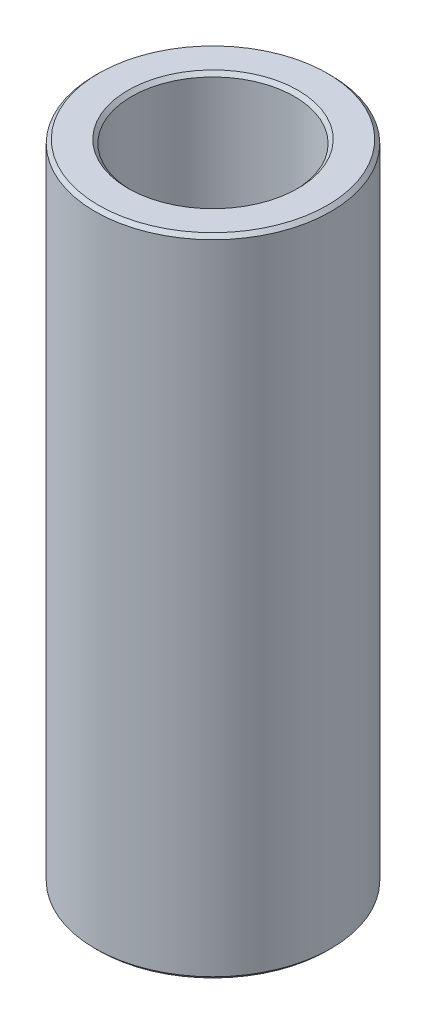
SolidWorks part; units mm, degrees
ref_plane "Front Plane" through (0, 0, 0) normal (0, 0, 1) x (1, 0, 0)
ref_plane "Top Plane" through (0, 0, 0) normal (0, 1, 0) x (1, 0, 0)
ref_plane "Right Plane" through (0, 0, 0) normal (1, 0, 0) x (0, 0, -1)
sketch "Sketch1" plane through (0, 0, 0) normal (0, 1, 0) x (1, 0, 0)
  circle A0 centre (0, 0) radius 55
  dimension "SLEEVE_OD" = 110
extrude "Boss-Extrude1" add sketch "Sketch1" along normal blind 300.9958
sketch "Sketch2" plane through (0, 0, 0) normal (0, 1, 0) x (1, 0, 0)
  circle A0 centre (0, 0) radius 37.9746
  dimension "BORE_D" = 75.9491
extrude "Cut-Extrude1" cut sketch "Sketch2" along normal through all
chamfer "Chamfer1" distance 1.671 angle 45 4 edges at (0, 300.9958, 37.9746) (0, 0, 37.9746) (0, 0, 55) (0, 300.9958, 55)
